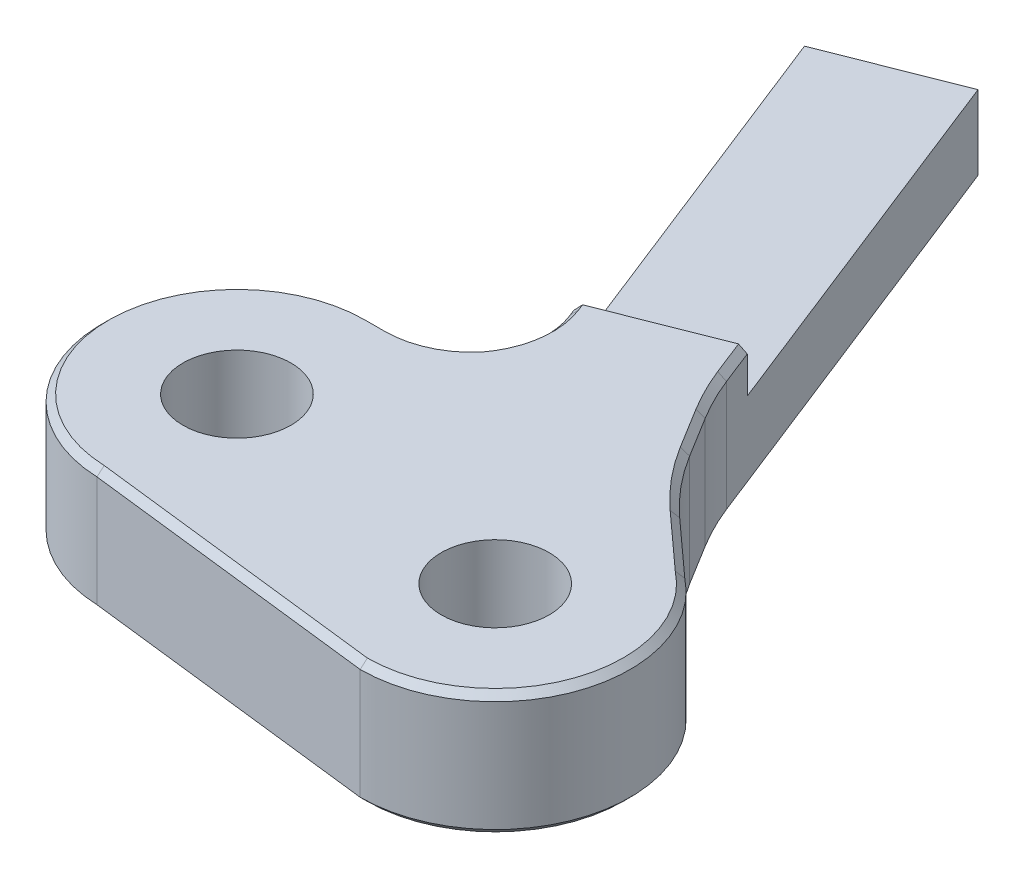
SolidWorks part; units mm, degrees
material "ﾒﾗﾐﾝ樹脂"
ref_plane "正面" through (0, 0, 0) normal (0, 0, 1) x (1, 0, 0)
ref_plane "平面" through (0, 0, 0) normal (0, 1, 0) x (1, 0, 0)
ref_plane "右側面" through (0, 0, 0) normal (1, 0, 0) x (0, 0, -1)
sketch "ｽｹｯﾁ1" plane through (0, 0, 0) normal (0, 1, 0) x (1, 0, 0)
  line L0 (14.9901, 43.6451) -> (63.9891, 43.9585) construction
  line L1 (83.8662, -8.9915) -> (72.8129, -7.6885)
  line L2 (83.8662, 2.7433) -> (86.9549, -0.0596)
  line L3 (83.8662, 2.7433) -> (81.7371, 6.2035)
  line L4 (81.7371, 6.2035) -> (75.3589, 22.3958)
  line L5 (75.3589, 22.3958) -> (70.7488, 20.5799)
  line L6 (70.7488, 20.5799) -> (77.0351, 4.6206)
  line L7 (73.0007, 2.3079) -> (75.1438, 2.3079)
  line L8 (75.1438, 2.3079) -> (77.0351, 4.6206)
  circle A0 centre (83.8662, -3.9915) radius 5
  circle A1 centre (73.0007, -2.6921) radius 5
  circle A2 centre (83.8662, -3.9915) radius 2
  circle A3 centre (73.0007, -2.6921) radius 2
  dimension "D1" = 49
extrude "ﾎﾞｽ - 押し出し1" add sketch "ｽｹｯﾁ1" along normal blind 4.6 contours A1 L1 A0 L2 L3 L4 L5 L6 L8 L7 | L1 A0 A2 | A1 A3 region at (83.3014, 0, 8.7825) region at (77.5318, 0, -7.8312) region at (68.143, 0, 2.6008)
sketch "ｽｹｯﾁ2" plane through (0, 4.6, 0) normal (0, 1, 0) x (1, 0, 0)
  line L0 (77.0351, 4.6206) -> (76.3021, 6.4814)
  line L1 (70.7488, 20.5799) -> (77.0351, 4.6206) construction
  line L2 (76.3021, 6.4814) -> (80.9123, 8.2974)
  line L3 (81.7371, 6.2035) -> (75.3589, 22.3958) construction
  line L4 (80.9123, 8.2974) -> (75.3589, 22.3958)
  line L5 (75.3589, 22.3958) -> (70.7488, 20.5799)
  line L6 (70.7488, 20.5799) -> (76.3021, 6.4814)
  line M7 (81.7371, 6.2035) -> (75.3589, 22.3958)
  line M8 (75.3589, 22.3958) -> (70.7488, 20.5799)
  line M9 (70.7488, 20.5799) -> (77.0351, 4.6206)
extrude "ｶｯﾄ - 押し出し1" cut sketch "ｽｹｯﾁ2" against normal blind 1.6 contours L2 M9 M7 M8 region at (75.8305, 4.6, -14.4386)
fillet "ﾌｨﾚｯﾄ1" radius 3 2 edges at (75.1438, 2.3, -2.3079) (77.0351, 2.3, -4.6206)
fillet "ﾌｨﾚｯﾄ2" radius 10 2 edges at (83.8662, 2.3, -2.7433) (81.7371, 2.3, -6.2035)
chamfer "面取り1" distance 0.25 angle 45 13 edges at (76.5702, 0, -4.7423) (74.9628, 0, -2.5767) (73.3612, 0, -2.3079) (68.0016, 0, 2.5981) (78.3395, 0, 8.34) (88.5916, 0, 5.6256) (85.9366, 0, -0.8645) (83.9435, 0, -2.8075) (82.661, 0, -4.7019) (81.772, 0, -6.2209) (78.386, 0, -14.711) (73.0538, 0, -21.4879) (73.5696, 0, -13.4186)
chamfer "面取り2" distance 0.25 angle 45 12 edges at (76.3462, 4.6, -6.3694) (76.5702, 4.6, -4.7423) (74.9628, 4.6, -2.5767) (73.3612, 4.6, -2.3079) (68.0016, 4.6, 2.5981) (78.3395, 4.6, 8.34) (88.5916, 4.6, 5.6256) (85.9366, 4.6, -0.8645) (83.9435, 4.6, -2.8075) (82.661, 4.6, -4.7019) (81.772, 4.6, -6.2209) (81.1627, 4.6, -7.6618)
